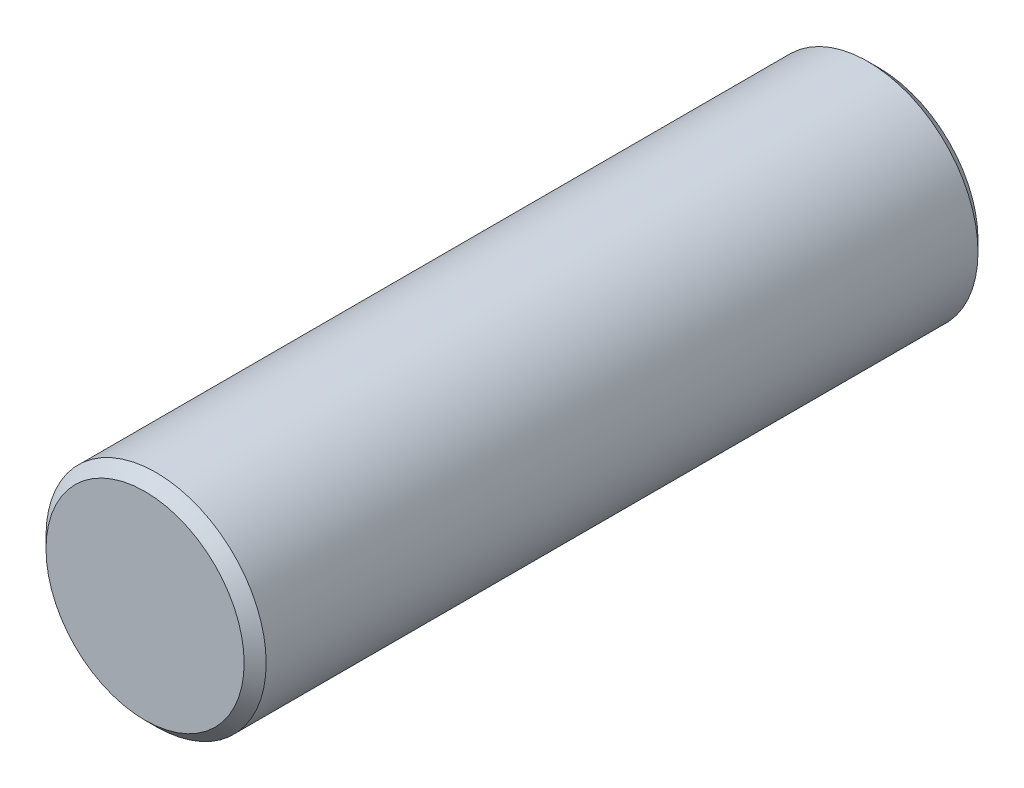
SolidWorks part; units mm, degrees
ref_plane "Piano frontale" through (0, 0, 0) normal (0, 0, 1) x (1, 0, 0)
ref_plane "Piano superiore" through (0, 0, 0) normal (0, 1, 0) x (1, 0, 0)
ref_plane "Piano destro" through (0, 0, 0) normal (1, 0, 0) x (0, 0, -1)
sketch "Schizzo1" plane through (0, 0, 0) normal (0, 0, 1) x (1, 0, 0)
  circle A0 centre (0, 0) radius 1.5
  dimension "D1" = 3
extrude "Estrusione-Estrusione1" add sketch "Schizzo1" along normal blind 5 and the other way blind 5
chamfer "Smusso1" distance 0.15 angle 45 2 edges at (1.5, 0, 5) (1.5, 0, -5)
